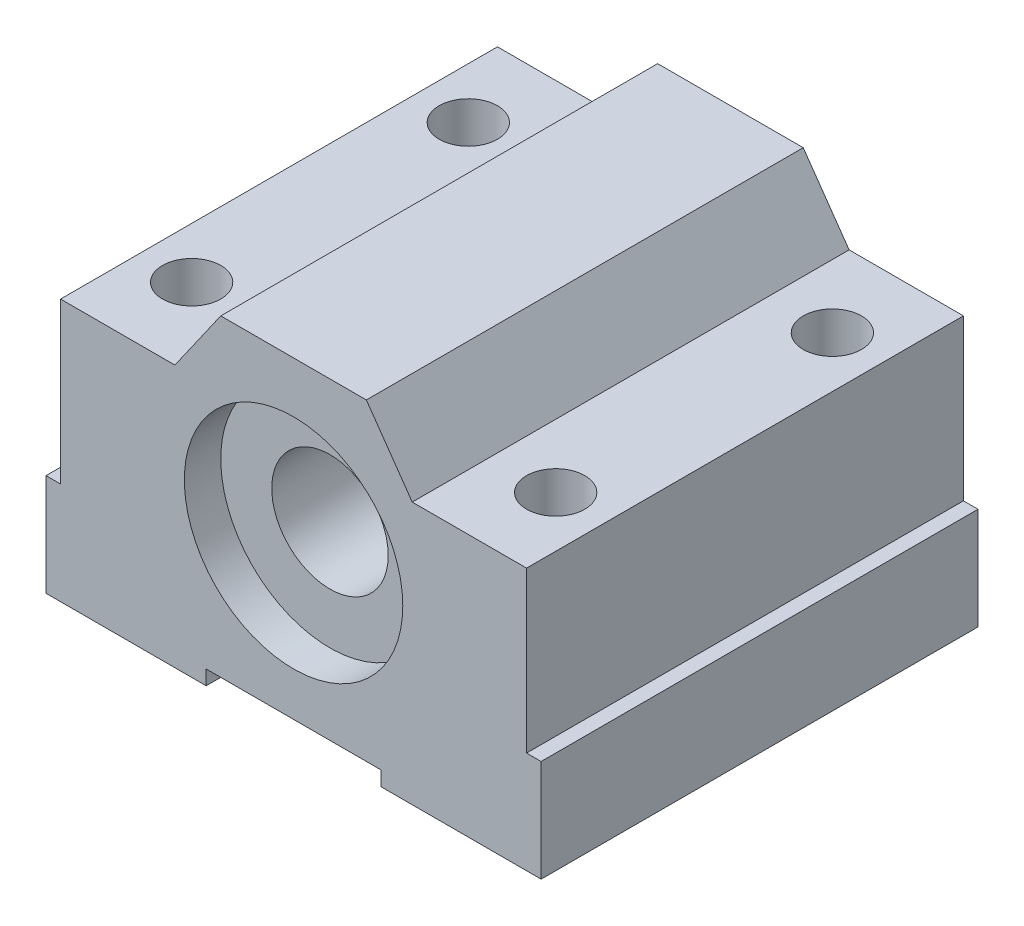
SolidWorks part; units mm, degrees
ref_plane "Front Plane" through (0, 0, 0) normal (0, 0, 1) x (1, 0, 0)
ref_plane "Top Plane" through (0, 0, 0) normal (0, 1, 0) x (1, 0, 0)
ref_plane "Right Plane" through (0, 0, 0) normal (1, 0, 0) x (0, 0, -1)
sketch "Sketch1" plane through (0, 0, 0) normal (0, 1, 0) x (1, 0, 0)
  line L0 (1, 30) -> (1, 0)
  line L1 (0, 0) -> (34, 0)
  line L2 (0, 0) -> (0, 30)
  line L3 (0, 30) -> (34, 30)
  line L4 (34, 0) -> (34, 30)
  line L5 (33, 30) -> (33, 0)
  line L6 (11, 30) -> (11, 0)
  line L7 (23, 30) -> (23, 0)
  dimension "D1" = 30
  dimension "D2" = 34
  dimension "D3" = 1
  dimension "D4" = 1
  dimension "D5" = 11
  dimension "D6" = 11
extrude "Boss-Extrude1" add sketch "Sketch1" along normal blind 1 contours L3 L7 L1 L5 | L3 L5 L1 L4 | L3 L2 L1 L0 | L6 L3 L0 L1 region at (6, 0, -15) region at (0.5, 0, -15) region at (28, 0, -15) region at (33.5, 0, -15)
extrude "Boss-Extrude4" add sketch "Sketch1<3>" along normal blind 6 from offset 1 contours L1 L4 L3 L2
sketch "Sketch1<3>" plane through (0, 0, 0) normal (0, 1, 0) x (1, 0, 0) same geometry as "Sketch1"
extrude "Boss-Extrude5" add sketch "Sketch1<4>" along normal blind 11 from surface contours L6 L3 L0 L1 | L3 L7 L1 L5 | L7 L3 L6 L1 region at (6, 0, -15) region at (17, 0, -15) region at (28, 0, -15) starting at face at (17, 7, -15)
sketch "Sketch1<4>" plane through (0, 0, 0) normal (0, 1, 0) x (1, 0, 0) same geometry as "Sketch1"
sketch "Sketch3" plane through (0, 18, 0) normal (0, 1, 0) x (1, 0, 0)
  line L0 (17, 30) -> (17, 0) construction
  line L1 (8.5, 30) -> (8.5, 0)
  line L2 (25.5, 30) -> (25.5, 0)
  line L4 (33, 30) -> (1, 30)
  line L5 (1, 30) -> (1, 0)
  line L6 (1, 0) -> (33, 0)
  line L7 (33, 0) -> (33, 30)
  line L8 (33, 30) -> (1, 30)
  line L9 (1, 30) -> (1, 0)
  line L10 (1, 0) -> (33, 0)
  line L11 (33, 0) -> (33, 30)
  line M8 (33, 30) -> (1, 30)
  line M10 (1, 0) -> (33, 0)
  dimension "D2" = 17
  dimension "D3" = 8.5
  dimension "D1" = 0
extrude "Boss-Extrude6" add sketch "Sketch3" along normal blind 4.5 contours L0 L10 L2 M8 | L0 L8 L1 M10 region at (21.25, 18, -15) region at (12.75, 18, -15)
chamfer "Chamfer1" distance 5 angle 35 2 edges at (25.5, 22.5, -15) (8.5, 22.5, -15) tangent propagation no first distance on face at (25.5, 20.25, -15) first distance on face at (8.5, 20.25, -15)
sketch "Sketch5" plane through (0, 0, 0) normal (0, 0, 1) x (1, 0, 0)
  line L0 (17, 4) -> (17, 1)
  line L1 (11, 1) -> (23, 1) construction
  line L2 (17, 22.5) -> (17, 19)
  line L3 (12.001, 22.5) -> (21.999, 22.5) construction
  circle A0 centre (17, 11.5) radius 7.5
  circle A1 centre (17, 11.5) radius 4
  dimension "D1" = 15
  dimension "D2" = 8
  dimension "D3" = 3
  dimension "D5" = 3.5
extrude "Cut-Extrude1" cut sketch "Sketch5" against normal blind 2.5 contours A0 A1 | A1 region at (22.1533, 6.3467, 0) region at (17, 11.5, 0)
extrude "Cut-Extrude2" cut sketch "Sketch5<3>" against normal through all contours A1 region at (17, 11.5, 0)
sketch "Sketch5<3>" plane through (0, 0, 0) normal (0, 0, 1) x (1, 0, 0) same geometry as "Sketch5"
extrude "Cut-Extrude4" cut sketch "Sketch5<4>" along normal blind 2.5 from surface contours A0 A1 | A1 region at (22.1533, 6.3467, 0) region at (17, 11.5, 0) starting at face at (21, 11.5, -30)
sketch "Sketch5<4>" plane through (0, 0, 0) normal (0, 0, 1) x (1, 0, 0) same geometry as "Sketch5"
sketch "Sketch6" plane through (0, 18, 0) normal (0, 1, 0) x (1, 0, 0)
  line L0 (25.1499, 30) -> (33, 30) construction
  line L1 (25.1499, 0) -> (33, 0) construction
  line L2 (33, 30) -> (33, 0) construction
  line L3 (17, 0) -> (17, 30) construction
  line L4 (12.001, 0) -> (21.999, 0) construction
  line L5 (21.999, 30) -> (12.001, 30) construction
  circle A0 centre (29.5, 24.5) radius 2
  circle A1 centre (29.5, 5.5) radius 2
  circle A2 centre (4.5, 24.5) radius 2
  circle A3 centre (4.5, 5.5) radius 2
  dimension "D1" = 4
  dimension "D2" = 5.5
  dimension "D5" = 3.5
  dimension "D6" = 4
  dimension "D3" = 5.5
  dimension "D4" = 3.5
extrude "Cut-Extrude5" cut sketch "Sketch6" against normal through all
